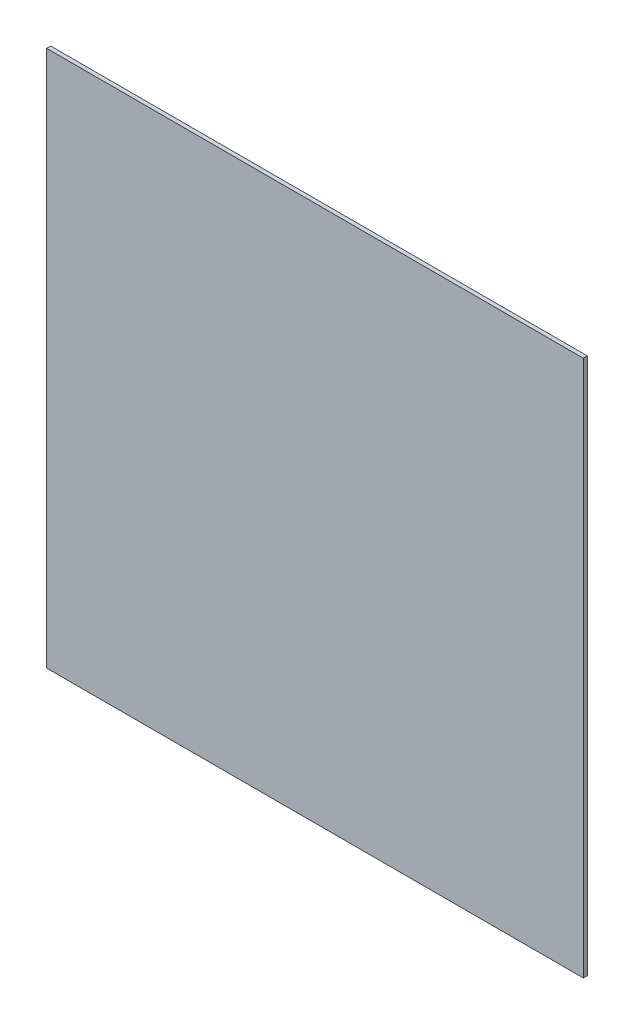
SolidWorks part; units mm, degrees
ref_plane "Ön Düzlem" through (0, 0, 0) normal (0, 0, 1) x (1, 0, 0)
ref_plane "Üst Düzlem" through (0, 0, 0) normal (0, 1, 0) x (1, 0, 0)
ref_plane "Sağ Düzlem" through (0, 0, 0) normal (1, 0, 0) x (0, 0, -1)
sketch "Çizim1" plane through (0, 0, 0) normal (0, 0, 1) x (1, 0, 0)
  line L1 (0, 0) -> (2000, 0)
  line L2 (0, 0) -> (0, -2000)
  line L3 (0, -2000) -> (2000, -2000)
  line L4 (2000, 0) -> (2000, -2000)
  dimension "D1" = 2000
  dimension "D2" = 2000
base flange "Taban-Flanş1" sketch "Çizim1" thickness 15 reverse thickness direction no parameters "D1"=4
sketch "Büküm-Çizgileri1" [suppressed] plane through (0, 0, 0) normal (0, 1, 0) x (1, 0, 0)
sketch "Sınırlandırma-Kutusu1" [suppressed] plane through (0, 0, 0) normal (0, 1, 0) x (1, 0, 0)
sheet metal parameters "Sac-Levha1" thickness 15 parameters "D1"=4
flat pattern "Düz-Çoğaltma1" [suppressed]
sketch "Büküm-Çizgileri2" plane through (0, 0, 0) normal (0, 1, 0) x (1, 0, 0)
sketch3d "Sınırlandırma-Kutusu2" [suppressed]
  line L0 (0, -2000, 0) -> (2000, -2000, 0) construction
  line L1 (0, 0, 0) -> (2000, 0, 0) construction
  line L2 (0, -2000, 0) -> (0, 0, 0) construction
  line L3 (2000, -2000, 0) -> (2000, 0, 0) construction
